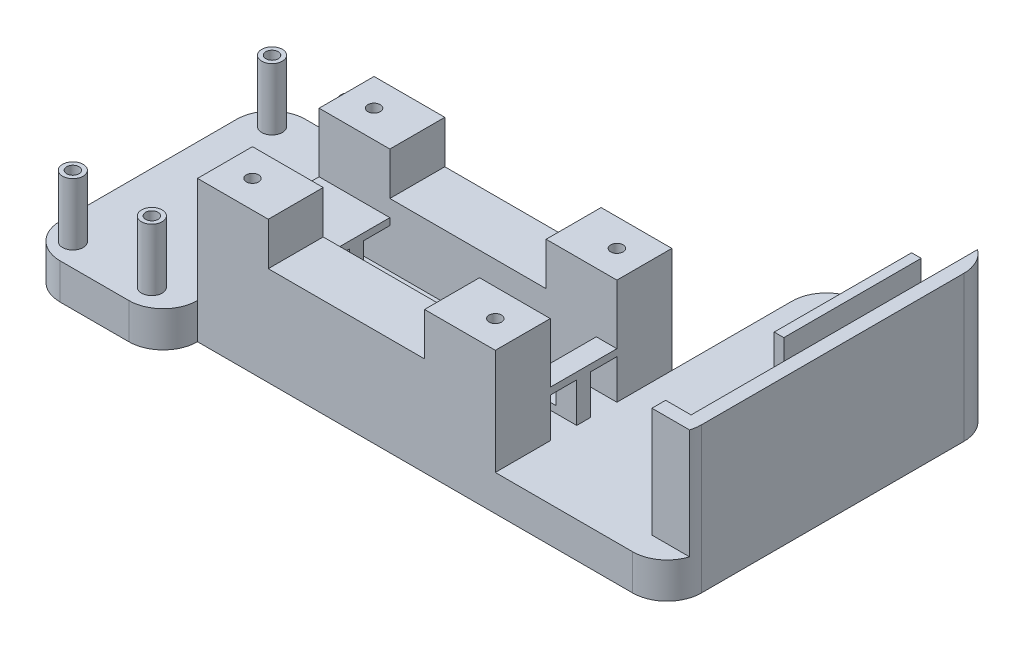
SolidWorks part; units mm, degrees
ref_plane "前视基准面" through (0, 0, 0) normal (0, 0, 1) x (1, 0, 0)
ref_plane "上视基准面" through (0, 0, 0) normal (0, 1, 0) x (1, 0, 0)
ref_plane "右视基准面" through (0, 0, 0) normal (1, 0, 0) x (0, 0, -1)
sketch "草图1" plane through (0, 0, 0) normal (0, 0, 1) x (1, 0, 0)
  line L1 (-42.1231, 25.5984) -> (44.5769, 25.5984)
  line L2 (-42.1231, 25.5984) -> (-42.1231, 5.5984)
  line L3 (-42.1231, 5.5984) -> (44.5769, 5.5984)
  line L4 (44.5769, 25.5984) -> (44.5769, 5.5984)
  line L5 (-21.5231, 25.5984) -> (23.9769, 25.5984)
  line L6 (-21.5231, 25.5984) -> (-21.5231, 13.1284)
  line L7 (-21.5231, 13.1284) -> (23.9769, 13.1284)
  line L8 (23.9769, 25.5984) -> (23.9769, 13.1284)
  dimension "D1" = 86.7
  dimension "D2" = 20
  dimension "D3" = 45.5
  dimension "D4" = 20.6
  dimension "D5" = 20.6
  dimension "D6" = 12.47
extrude "凸台-拉伸1" add sketch "草图1" along normal blind 16 contours L1 L8 L7 L6 L2 L3 L4 region at (-31.8231, 24.7086, 0)
sketch "草图2" plane through (0, 25.5984, 0) normal (0, 1, 0) x (1, 0, 0)
  line L0 (23.9769, -8) -> (28.5769, -8) construction
  line L1 (23.9769, -16) -> (23.9769, 0) construction
  line L2 (28.5769, -8) -> (28.5769, 0) construction
  line L3 (23.9769, 0) -> (44.5769, 0) construction
  line L4 (28.5769, 0) -> (28.5769, -16) construction
  line L5 (23.9769, -16) -> (44.5769, -16) construction
  line L7 (28.5769, 0) -> (44.5769, -16) construction
  line L8 (44.5769, 0) -> (28.5769, -16) construction
  point P16 (36.5769, -8)
  dimension "D1" = 4.6
hole_wizard "Ø1.0mm 暗销孔1" positions "草图2" profile "草图3" hole size "Ø1.0" standard "GB" end condition through all
sketch "草图3" plane through (36.5769, 25.5984, 8) normal (1, 0, 0) x (0, 0, 1)
  line L0 (0, 0) -> (0, 20)
  line L1 (0, 20) -> (1.8, 20)
  line L2 (1.8, 20) -> (1.8, 0)
  line L5 (1.8, 0) -> (0, 0)
  line L11 (0, -6.35) -> (0, 107.95) construction
  dimension "通孔孔直径" = 3.6
  dimension "通孔孔深度" = 20
sketch "草图4" plane through (0, 25.5984, 0) normal (0, 1, 0) x (1, 0, 0)
  line L0 (-21.5231, -8) -> (-26.1231, -8) construction
  line L1 (-21.5231, -16) -> (-21.5231, 0) construction
  line L2 (-26.1231, -8) -> (-26.1231, 0) construction
  line L3 (-42.1231, 0) -> (-21.5231, 0) construction
  line L4 (-26.1231, 0) -> (-26.1231, -16) construction
  line L5 (-42.1231, -16) -> (-21.5231, -16) construction
  line L6 (-42.1231, 0) -> (-26.1231, -16) construction
  line L7 (-26.1231, -16) -> (-26.1231, 0) construction
  line L8 (-26.1231, 0) -> (-42.1231, -16) construction
  point P15 (-34.1231, -8)
  dimension "D1" = 4.6
hole_wizard "Ø1.0mm 暗销孔2" positions "草图4" profile "草图5" hole size "Ø1.0" standard "GB" end condition through all
sketch "草图5" plane through (-34.1231, 25.5984, 8) normal (1, 0, 0) x (0, 0, 1)
  line L0 (0, 0) -> (0, 20)
  line L1 (0, 20) -> (1.8, 20)
  line L2 (1.8, 20) -> (1.8, 0)
  line L5 (1.8, 0) -> (0, 0)
  line L11 (0, -6.35) -> (0, 107.95) construction
  dimension "通孔孔直径" = 3.6
  dimension "通孔孔深度" = 20
sketch "草图7" plane through (0, 25.5984, 0) normal (0, 1, 0) x (1, 0, 0)
sketch "草图8" plane through (0, 5.5984, 0) normal (0, -1, 0) x (1, 0, 0)
  line L1 (-42.1231, 16) -> (44.5769, 16)
  line L2 (-42.1231, 16) -> (-42.1231, 0)
  line L3 (-42.1231, 0) -> (44.5769, 0)
  line L4 (44.5769, 16) -> (44.5769, 0)
extrude "凸台-拉伸2" add sketch "草图8" along normal blind 21.2
sketch "草图9" plane through (0, 0, 0) normal (0, 0, -1) x (-1, 0, 0)
  line L0 (42.1231, 25.5984) -> (42.1231, -15.6016) construction
  line L1 (-44.5769, -15.6016) -> (42.1231, -15.6016)
  line L2 (-44.5769, -15.6016) -> (-44.5769, -5.2016)
  line L3 (-44.5769, -5.2016) -> (42.1231, -5.2016)
  line L4 (42.1231, -15.6016) -> (42.1231, -5.2016)
  dimension "D1" = 10.4
extrude "凸台-拉伸3" add sketch "草图9" along normal blind 9.7
sketch "草图15" plane through (0, -5.2016, 0) normal (0, 1, 0) x (1, 0, 0)
  line L5 (-42.1231, 9.7) -> (-21.5231, 9.7)
  line L6 (-42.1231, 9.7) -> (-42.1231, 7.7)
  line L7 (-42.1231, 7.7) -> (-21.5231, 7.7)
  line L8 (-21.5231, 9.7) -> (-21.5231, 7.7)
  dimension "D1" = 2
extrude "凸台-拉伸8" add sketch "草图15" along normal blind 13.5
sketch "草图16" plane through (0, 0, -9.7) normal (0, 0, -1) x (-1, 0, 0)
  line L0 (42.1231, -15.6016) -> (42.1231, 8.2984) construction
  line L1 (21.5231, 8.2984) -> (42.1231, 8.2984)
  line L2 (21.5231, 8.2984) -> (21.5231, 6.2984)
  line L3 (21.5231, 6.2984) -> (42.1231, 6.2984)
  line L4 (42.1231, 8.2984) -> (42.1231, 6.2984)
  dimension "D1" = 2
extrude "凸台-拉伸9" add sketch "草图16" against normal blind 10.5
mirror "镜向20" about plane through (0, 0, -9.7) normal (0, 0, 1) of "Ø1.0mm 暗销孔2", "Ø1.0mm 暗销孔1", "凸台-拉伸3", "凸台-拉伸1", "凸台-拉伸2", "凸台-拉伸8", "凸台-拉伸9"
sketch "草图19" plane through (44.5769, 0, 0) normal (1, 0, 0) x (0, 0, -1)
  line L0 (35.4, 25.5984) -> (35.4, -15.6016) construction
  line L1 (-16, -15.6016) -> (35.4, -15.6016)
  line L2 (-16, -15.6016) -> (-16, -5.2016)
  line L3 (-16, -5.2016) -> (35.4, -5.2016)
  line L4 (35.4, -15.6016) -> (35.4, -5.2016)
  line L5 (19.4, -5.2016) -> (0, -5.2016) construction
  dimension "D1" = 0
  dimension "D2" = 10.4
extrude "凸台-拉伸10" add sketch "草图19" along normal blind 50
sketch "草图25" plane through (0, 0, -35.4) normal (0, 0, -1) x (-1, 0, 0)
  line L0 (-94.5769, -15.6016) -> (42.1231, -15.6016) construction
  line L1 (-94.5769, -5.2016) -> (-44.5769, -5.2016)
  line L2 (-94.5769, -5.2016) -> (-94.5769, -15.6016)
  line L3 (-94.5769, -15.6016) -> (-44.5769, -15.6016)
  line L4 (-44.5769, -5.2016) -> (-44.5769, -15.6016)
extrude "凸台-拉伸11" add sketch "草图25" along normal blind 45
sketch "草图26" plane through (0, -5.2016, 0) normal (0, 1, 0) x (1, 0, 0)
  line L0 (44.5769, 0) -> (94.5769, 0) construction
  line L1 (94.5769, 80.4) -> (94.5769, -16) construction
  line L2 (44.5769, 80.4) -> (94.5769, 80.4) construction
  line L7 (83.1769, -9) -> (94.5769, -9)
  line L8 (83.1769, -9) -> (83.1769, -5)
  line L9 (83.1769, -5) -> (90.5769, -5)
  line L10 (94.5769, -9) -> (94.5769, -5)
  line L12 (94.5769, -5) -> (94.5769, 80.4)
  line L13 (94.5769, 80.4) -> (90.5769, 80.4)
  line L14 (90.5769, -5) -> (90.5769, 80.4)
  line L15 (83.1769, -5) -> (83.1769, 28) construction
  line L29 (83.1769, 28) -> (84.5769, 28)
  line L31 (83.1769, 68) -> (84.5769, 68)
  line L32 (84.5769, 28) -> (84.5769, 68)
  line L36 (83.1769, 68) -> (83.1769, 83.3786) construction
  line L37 (83.1769, 28) -> (81.7769, 28)
  line L39 (83.1769, 68) -> (81.7769, 68)
  line L40 (81.7769, 28) -> (81.7769, 68)
  dimension "D1" = 4
  dimension "D2" = 5
  dimension "D3" = 4
  dimension "D4" = 7.4
  dimension "D5" = 1.4
  dimension "D6" = 28
  dimension "D7" = 1.4
  dimension "D8" = 40
  dimension "D9" = 6
extrude "凸台-拉伸12" add sketch "草图26" along normal blind 32
sketch "草图28" plane through (0, -5.2016, 0) normal (0, 1, 0) x (1, 0, 0)
  line L0 (84.5769, 28) -> (84.5769, 68) construction
  line L13 (90.5769, -5) -> (84.5769, -5)
  line L14 (90.5769, -5) -> (90.5769, 80.4)
  line L15 (90.5769, 80.4) -> (84.5769, 80.4)
  line L16 (84.5769, 28) -> (84.5769, 80.4)
  line L17 (94.5769, 80.4) -> (90.5769, 80.4) construction
  line L19 (84.5769, -5) -> (82.5769, -5)
  line L21 (84.5769, 28) -> (82.5769, 28)
  line L22 (82.5769, -5) -> (82.5769, 28)
  dimension "D1" = 6
  dimension "D2" = 0
  dimension "D3" = 2
  dimension "D4" = 33
extrude "切除-拉伸1" cut sketch "草图28" against normal blind 5
sketch "草图29" plane through (-42.1231, 0, 0) normal (-1, 0, 0) x (0, 0, 1)
  line L0 (-35.4, 25.5984) -> (-35.4, -15.6016) construction
  line L1 (-35.4, -5.1986) -> (16, -5.1986)
  line L2 (-35.4, -5.1986) -> (-35.4, -15.6016)
  line L3 (-35.4, -15.6016) -> (16, -15.6016)
  line L4 (16, -5.1986) -> (16, -15.6016)
extrude "凸台-拉伸13" add sketch "草图29" along normal blind 40
sketch "草图32" plane through (0, 0, -35.4) normal (0, 0, -1) x (-1, 0, 0)
  line L1 (42.1231, -5.1986) -> (82.1231, -5.1986)
  line L2 (42.1231, -5.1986) -> (42.1231, -15.6016)
  line L3 (42.1231, -15.6016) -> (82.1231, -15.6016)
  line L4 (82.1231, -5.1986) -> (82.1231, -15.6016)
extrude "凸台-拉伸14" add sketch "草图32" along normal blind 10
sketch "草图33" plane through (0, 0, 16) normal (0, 0, 1) x (1, 0, 0)
  line L0 (94.5769, -15.6016) -> (-82.1231, -15.6016) construction
  line L1 (-82.1231, -5.1986) -> (-42.1231, -5.1986)
  line L2 (-82.1231, -5.1986) -> (-82.1231, -15.6016)
  line L3 (-82.1231, -15.6016) -> (-42.1231, -15.6016)
  line L4 (-42.1231, -5.1986) -> (-42.1231, -15.6016)
extrude "凸台-拉伸15" add sketch "草图33" along normal blind 10
sketch "草图34" plane through (0, -5.1986, 0) normal (0, 1, 0) x (1, 0, 0)
  line L0 (-42.1231, 9.7) -> (-82.1231, 9.7) construction
  line L1 (-55.1231, 38.7) -> (-72.1231, 38.7)
  line L2 (-52.1231, 35.7) -> (-52.1231, -16.3)
  line L3 (-55.1231, -19.3) -> (-72.1231, -19.3)
  line L4 (-75.1231, 35.7) -> (-75.1231, -16.3)
  line L5 (-42.1231, 7.7) -> (-42.1231, 11.7) construction
  line L6 (-82.1231, -26) -> (-82.1231, 45.4) construction
  line L7 (-42.1231, 11.7) -> (-42.1231, 19.4) construction
  circle A0 centre (-52.1231, 38.7) radius 3
  circle A1 centre (-52.1231, -19.3) radius 3
  circle A2 centre (-75.1231, 38.7) radius 3
  circle A3 centre (-75.1231, -19.3) radius 3
  dimension "D4" = 6
  dimension "D5" = 6
  dimension "D7" = 6
  dimension "D8" = 6
  dimension "D1" = 23
  dimension "D2" = 58
  dimension "D3" = 29
  dimension "D6" = 10
extrude "凸台-拉伸16" add sketch "草图34" along normal blind 18 contours A0 | A2 | A1 | A3 region at (-52.1231, -5.1986, -38.7) region at (-75.1231, -5.1986, -38.7) region at (-52.1231, -5.1986, 19.3) region at (-75.1231, -5.1986, 19.3)
sketch "草图35" plane through (0, 12.8014, 0) normal (0, 1, 0) x (1, 0, 0)
  point P0 (-52.1231, 38.7)
hole_wizard "Ø1.0mm 暗销孔3" positions "草图35" profile "草图36" hole size "Ø1.0" standard "GB" end condition through all
sketch "草图36" plane through (-52.1231, 12.8014, -38.7) normal (1, 0, 0) x (0, 0, 1)
  line L0 (0, 0) -> (0, 28.403)
  line L1 (0, 28.403) -> (1.8, 28.403)
  line L2 (1.8, 28.403) -> (1.8, 0)
  line L5 (1.8, 0) -> (0, 0)
  line L11 (0, -6.35) -> (0, 107.95) construction
  dimension "通孔孔直径" = 3.6
  dimension "通孔孔深度" = 28.403
sketch "草图37" plane through (0, 12.8014, 0) normal (0, 1, 0) x (1, 0, 0)
  line L0 (-75.1231, 41.7) -> (-75.1231, 35.7) construction
  line L1 (-75.1231, 35.7) -> (-72.1231, 38.7) construction
  line L2 (-72.1231, 38.7) -> (-78.1231, 38.7) construction
  line L3 (-75.1231, -16.3) -> (-75.1231, -22.3) construction
  line L4 (-75.1231, -22.3) -> (-72.1231, -19.3) construction
  line L5 (-72.1231, -19.3) -> (-78.1231, -19.3) construction
  line L6 (-52.1231, -16.3) -> (-52.1231, -22.3) construction
  line L7 (-52.1231, -22.3) -> (-49.1231, -19.3) construction
  line L8 (-49.1231, -19.3) -> (-55.1231, -19.3) construction
  circle A0 centre (-75.1231, 38.7) radius 3 construction
  circle A1 centre (-75.1231, 38.7) radius 3 construction
  circle A2 centre (-75.1231, -19.3) radius 3 construction
  circle A3 centre (-75.1231, -19.3) radius 3 construction
  circle A4 centre (-52.1231, -19.3) radius 3 construction
  circle A5 centre (-52.1231, -19.3) radius 3 construction
  point P29 (-75.1231, 38.7)
  point P31 (-75.1231, -19.3)
  point P33 (-52.1231, -19.3)
hole_wizard "Ø1.0mm 暗销孔4" positions "草图37" profile "草图38" hole size "Ø1.0" standard "GB" end condition through all
sketch "草图38" plane through (-52.1231, 12.8014, 19.3) normal (1, 0, 0) x (0, 0, 1)
  line L0 (0, 0) -> (0, 28.403)
  line L1 (0, 28.403) -> (1.8, 28.403)
  line L2 (1.8, 28.403) -> (1.8, 0)
  line L5 (1.8, 0) -> (0, 0)
  line L11 (0, -6.35) -> (0, 107.95) construction
  dimension "通孔孔直径" = 3.6
  dimension "通孔孔深度" = 28.403
sketch "草图39" plane through (0, -5.1986, 0) normal (0, 1, 0) x (1, 0, 0)
  line L0 (-75.1231, 38.7) -> (-52.1231, 38.7) construction
  line L1 (-52.1231, 38.7) -> (-52.1231, -19.3) construction
fillet "圆角1" radius 10 6 edges at (44.5769, -10.4016, -80.4) (94.5769, -10.4016, 16) (-42.1231, -10.4001, -45.4) (-42.1231, -10.4001, 26) (-82.1231, -10.4001, -45.4) (-82.1231, -10.4001, 26)
fillet "圆角2" radius 10 1 edges at (94.5769, 5.5984, -80.4)
sketch "草图40" plane through (0, -5.2016, 0) normal (0, 1, 0) x (1, 0, 0)
  line L0 (23.9769, 19.4) -> (23.9769, 0) construction
  line L1 (44.5769, 19.4) -> (44.5769, 0) construction
  line L2 (23.9769, 9.7) -> (44.5769, 9.7) construction
  line L4 (38.5769, 11.7) -> (44.5769, 11.7)
  line L5 (38.5769, 11.7) -> (38.5769, 7.7)
  line L6 (38.5769, 7.7) -> (44.5769, 7.7)
  line L7 (44.5769, 11.7) -> (44.5769, 7.7)
  dimension "D1" = 6
  dimension "D2" = 4
  dimension "D3" = 2
extrude "凸台-拉伸17" add sketch "草图40" along normal blind 11.5
sketch "草图42" plane through (0, 6.2984, 0) normal (0, 1, 0) x (1, 0, 0)
  line L0 (38.5769, 9.7) -> (44.5769, 9.7) construction
  line L1 (38.5769, 11.7) -> (38.5769, 7.7) construction
  line L2 (44.5769, 7.7) -> (44.5769, 11.7) construction
  line L3 (41.5769, 11.7) -> (41.5769, 7.7) construction
  line L4 (44.5769, 11.7) -> (38.5769, 11.7) construction
  line L5 (38.5769, 7.7) -> (44.5769, 7.7) construction
  line L7 (38.5769, 0) -> (44.5769, 0)
  line L8 (38.5769, 0) -> (38.5769, 19.4)
  line L9 (38.5769, 19.4) -> (44.5769, 19.4)
  line L10 (44.5769, 0) -> (44.5769, 19.4)
  line L11 (38.5769, 0) -> (44.5769, 19.4) construction
  line L12 (38.5769, 19.4) -> (44.5769, 0) construction
  point P12 (41.5769, 9.7)
  dimension "D1" = 19.4
extrude "凸台-拉伸18" add sketch "草图42" along normal blind 2
sketch "草图44" plane through (0, -5.2016, 0) normal (0, 1, 0) x (1, 0, 0)
  line L0 (-21.5231, 11.7) -> (38.5769, 11.7) construction
  line L1 (-21.5231, 7.7) -> (38.5769, 7.7) construction
  line L2 (-21.5231, 7.7) -> (-21.5231, 11.7) construction
sketch "草图45" plane through (-42.1231, 0, 0) normal (-1, 0, 0) x (0, 0, 1)
  line L0 (-38.7, -5.1986) -> (19.3, -5.1986) construction
  line L1 (-11.7, 6.2984) -> (-7.7, 6.2984)
  line L2 (-11.7, 6.2984) -> (-11.7, -5.1986)
  line L3 (-11.7, -5.1986) -> (-7.7, -5.1986)
  line L4 (-7.7, 6.2984) -> (-7.7, -5.1986)
  line L5 (-7.7, 6.2984) -> (-7.7, -5.1986) construction
sketch "草图46" plane through (0, -5.2016, 0) normal (0, 1, 0) x (1, 0, 0)
  line L1 (-21.5231, 11.7) -> (38.5769, 11.7)
  line L2 (-21.5231, 11.7) -> (-21.5231, 7.7)
  line L3 (-21.5231, 7.7) -> (38.5769, 7.7)
  line L4 (38.5769, 11.7) -> (38.5769, 7.7)
extrude "凸台-拉伸19" add sketch "草图46" along normal blind 2
